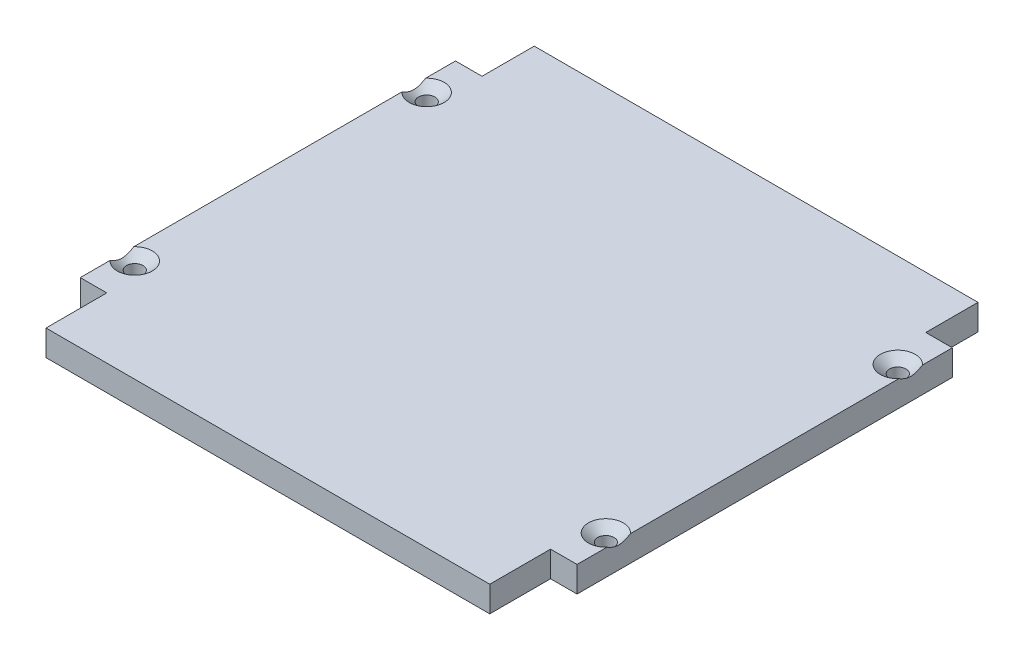
SolidWorks part; units mm, degrees
ref_plane "Front Plane" through (0, 0, 0) normal (0, 0, 1) x (1, 0, 0)
ref_plane "Top Plane" through (0, 0, 0) normal (0, 1, 0) x (1, 0, 0)
ref_plane "Right Plane" through (0, 0, 0) normal (1, 0, 0) x (0, 0, -1)
sketch "Sketch1" plane through (0, 0, 0) normal (0, 1, 0) x (1, 0, 0)
  line L0 (-41.1226, 44.45) -> (41.1226, 44.45)
  line L1 (41.1226, 44.45) -> (41.1226, 34.7726)
  line L2 (41.1226, 34.7726) -> (46.0375, 34.7726)
  line L3 (46.0375, 34.7726) -> (46.0375, -34.7726)
  line L4 (46.0375, -34.7726) -> (41.1226, -34.7726)
  line L5 (41.1226, -34.7726) -> (41.1226, -46.0375)
  line L6 (41.1226, -46.0375) -> (-41.1226, -46.0375)
  line L7 (0, -1000) -> (0, 49000) construction
  line L8 (-41.1226, -34.7726) -> (-41.1226, -46.0375)
  line L9 (-46.0375, -34.7726) -> (-41.1226, -34.7726)
  line L10 (-46.0375, 34.7726) -> (-46.0375, -34.7726)
  line L11 (-41.1226, 34.7726) -> (-46.0375, 34.7726)
  line L12 (-41.1226, 44.45) -> (-41.1226, 34.7726)
  circle A0 centre (43.6562, 27.051) radius 1.524
  circle A1 centre (43.6562, -27.051) radius 1.524
  circle A2 centre (-43.6562, -27.051) radius 1.524
  circle A3 centre (-43.6562, 27.051) radius 1.524
  point P9 (46.0375, 0)
  point P21 (0, -46.0375)
  point P26 (0, 44.45)
  dimension "D6" = 3.048
  dimension "D1" = 4.9149
  dimension "D2" = 9.6774
  dimension "D3" = 90.4875
  dimension "D4" = 7.7216
  dimension "D5" = 7.7216
  dimension "D7" = 2.3813
  dimension "D8" = 92.075
  dimension "D9" = 69.5452
extrude "Boss-Extrude1" add sketch "Sketch1" along normal blind 4.7625
chamfer "Chamfer1" distance 1.7145 angle 41 4 edges at (43.6562, 4.7625, -25.527) (43.6562, 4.7625, 28.575) (-43.6562, 4.7625, -28.575) (-43.6562, 4.7625, 25.527) first distance on face at (-43.6562, 4.7625, 25.527)
